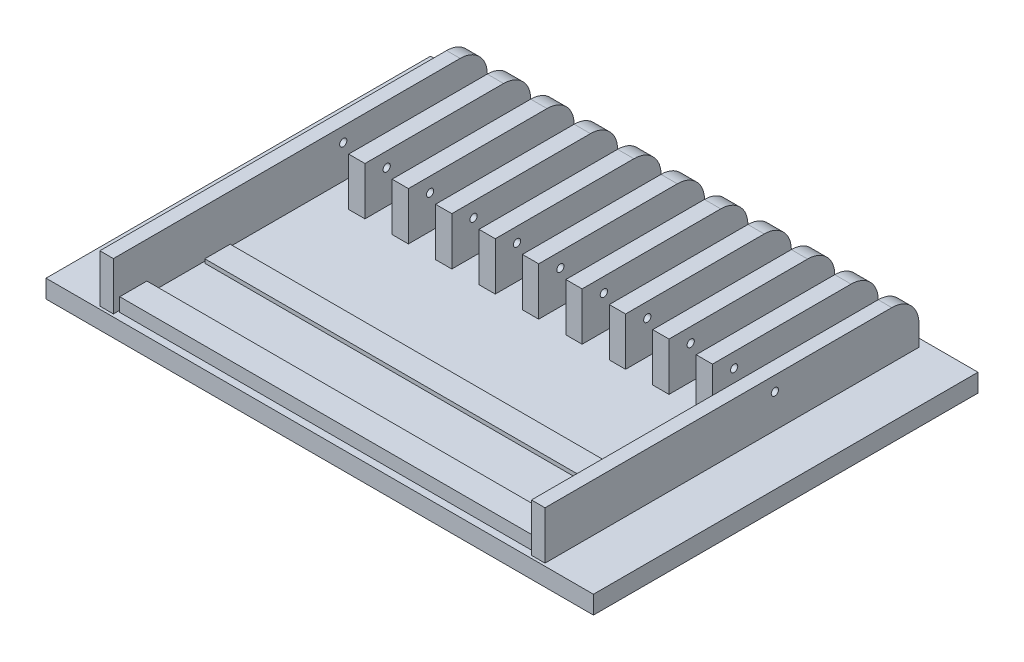
SolidWorks part; units mm, degrees
material "Maple"
ref_plane "Front Plane" through (0, 0, 0) normal (0, 0, 1) x (1, 0, 0)
ref_plane "Top Plane" through (0, 0, 0) normal (0, 1, 0) x (1, 0, 0)
ref_plane "Right Plane" through (0, 0, 0) normal (1, 0, 0) x (0, 0, -1)
sketch "Sketch1" plane through (0, 0, 0) normal (0, 1, 0) x (1, 0, 0)
  line L1 (302.5, -212.5) -> (-302.5, -212.5)
  line L2 (302.5, -212.5) -> (302.5, 212.5)
  line L3 (302.5, 212.5) -> (-302.5, 212.5)
  line L4 (-302.5, -212.5) -> (-302.5, 212.5)
  line L5 (302.5, -212.5) -> (-302.5, 212.5) construction
  line L6 (302.5, 212.5) -> (-302.5, -212.5) construction
  point P0 (0, 0)
  dimension "D1" = 605
  dimension "D2" = 425
extrude "Boss-Extrude1" add sketch "Sketch1" against normal blind 20
sketch "Sketch2" plane through (0, 0, 0) normal (1, 0, 0) x (0, 0, -1)
  line L0 (-212.5, -20) -> (-212.5, 0) construction
  line L1 (203.7, 0) -> (-209.5, 0)
  line L2 (203.7, 0) -> (203.7, 23)
  line L3 (173.7, 53) -> (-209.5, 53)
  line L4 (-209.5, 0) -> (-209.5, 53)
  line L5 (-212.5, 0) -> (212.5, 0) construction
  line L6 (212.5, -20) -> (212.5, 0) construction
  arc A0 (203.7, 23) -> (173.7, 53) centre (173.7, 23) ccw
  point P9 (0, 0)
  point P10 (194.2218, 0)
  dimension "D1" = 30
  dimension "D2" = 53
  dimension "D3" = 3
  dimension "D4" = 8.8
extrude "Boss-Extrude2" add sketch "Sketch2" along normal mid plane 492
sketch "Sketch3" plane through (0, 0, 209.5) normal (0, 0, 1) x (1, 0, 0)
  line L0 (246, 53) -> (-246, 53) construction
  line L1 (-231, 0) -> (-201, 0)
  line L2 (-231, 0) -> (-231, 53)
  line L3 (-231, 53) -> (-201, 53)
  line L4 (-201, 0) -> (-201, 53)
  line L5 (-231, 0) -> (-201, 53) construction
  line L6 (-231, 53) -> (-201, 0) construction
  line L7 (246, 0) -> (-246, 0) construction
  line L8 (0, 0) -> (0, 53) construction
  line L9 (-183, 0) -> (-183, 53)
  line L10 (-183, 53) -> (-153, 0) construction
  line L11 (-183, 0) -> (-153, 53) construction
  line L12 (-153, 0) -> (-153, 53)
  line L13 (-183, 53) -> (-153, 53)
  line L14 (-183, 0) -> (-153, 0)
  line L15 (-135, 0) -> (-135, 53)
  line L16 (-135, 53) -> (-105, 0) construction
  line L17 (-135, 0) -> (-105, 53) construction
  line L18 (-105, 0) -> (-105, 53)
  line L19 (-135, 53) -> (-105, 53)
  line L20 (-135, 0) -> (-105, 0)
  line L21 (-87, 0) -> (-87, 53)
  line L22 (-87, 53) -> (-57, 0) construction
  line L23 (-87, 0) -> (-57, 53) construction
  line L24 (-57, 0) -> (-57, 53)
  line L25 (-87, 53) -> (-57, 53)
  line L26 (-87, 0) -> (-57, 0)
  line L27 (-39, 0) -> (-39, 53)
  line L28 (-39, 53) -> (-9, 0) construction
  line L29 (-39, 0) -> (-9, 53) construction
  line L30 (-9, 0) -> (-9, 53)
  line L31 (-39, 53) -> (-9, 53)
  line L32 (-39, 0) -> (-9, 0)
  line L33 (9, 0) -> (9, 53)
  line L34 (9, 53) -> (39, 0) construction
  line L35 (9, 0) -> (39, 53) construction
  line L36 (39, 0) -> (39, 53)
  line L37 (9, 53) -> (39, 53)
  line L38 (9, 0) -> (39, 0)
  line L39 (57, 0) -> (57, 53)
  line L40 (57, 53) -> (87, 0) construction
  line L41 (57, 0) -> (87, 53) construction
  line L42 (87, 0) -> (87, 53)
  line L43 (57, 53) -> (87, 53)
  line L44 (57, 0) -> (87, 0)
  line L45 (105, 0) -> (105, 53)
  line L46 (105, 53) -> (135, 0) construction
  line L47 (105, 0) -> (135, 53) construction
  line L48 (135, 0) -> (135, 53)
  line L49 (105, 53) -> (135, 53)
  line L50 (105, 0) -> (135, 0)
  line L51 (153, 0) -> (153, 53)
  line L52 (153, 53) -> (183, 0) construction
  line L53 (153, 0) -> (183, 53) construction
  line L54 (183, 0) -> (183, 53)
  line L55 (153, 53) -> (183, 53)
  line L56 (153, 0) -> (183, 0)
  line L57 (201, 0) -> (201, 53)
  line L58 (201, 53) -> (231, 0) construction
  line L59 (201, 0) -> (231, 53) construction
  line L60 (231, 0) -> (231, 53)
  line L61 (201, 53) -> (231, 53)
  line L62 (201, 0) -> (231, 0)
  line L63 (-216, 26.5) -> (-168, 26.5) construction
  line L64 (0, 53) -> (-9, 53) construction
  line L65 (0, 53) -> (9, 53) construction
  point P0 (-216, 26.5)
  point P12 (-168, 26.5)
  point P18 (-120, 26.5)
  point P23 (-72, 26.5)
  point P28 (-24, 26.5)
  point P33 (24, 26.5)
  point P38 (72, 26.5)
  point P43 (120, 26.5)
  point P48 (168, 26.5)
  point P53 (216, 26.5)
  dimension "D1" = 30
  dimension "D3" = 48
  dimension "D2" = 10
extrude "Cut-Extrude1" cut sketch "Sketch3" against normal through all
sketch "Sketch4" plane through (-246, 0, 0) normal (-1, 0, 0) x (0, 0, 1)
  line L0 (209.5, 0) -> (-203.7, 0) construction
  line L1 (209.5, 53) -> (209.5, 0) construction
  circle A0 centre (-44.5, 37) radius 4
  dimension "D1" = 37
  dimension "D2" = 254
  dimension "D3" = 8
extrude "Cut-Extrude2" cut sketch "Sketch4" against normal through all
sketch "Sketch5" plane through (0, 0, 0) normal (1, 0, 0) x (0, 0, -1)
  line L0 (-212.5, 0) -> (212.5, 0) construction
  line L1 (-209.5, 53) -> (20.5, 53)
  line L2 (-209.5, 53) -> (-209.5, 0)
  line L3 (-209.5, 0) -> (20.5, 0)
  line L4 (20.5, 53) -> (20.5, 0)
  dimension "D1" = 230
extrude "Cut-Extrude3" cut sketch "Sketch5" against normal mid plane 440
sketch "Sketch6" plane through (0, 0, 0) normal (0, 1, 0) x (1, 0, 0)
  line L0 (0, 0) -> (0, -212.5) construction
  line L1 (-302.5, -212.5) -> (302.5, -212.5) construction
  line L2 (-231, -209.5) -> (-246, -209.5) construction
  line L3 (229, -174.5) -> (-229, -174.5)
  line L4 (229, -174.5) -> (229, -204.5)
  line L5 (229, -204.5) -> (-229, -204.5)
  line L6 (-229, -174.5) -> (-229, -204.5)
  line L7 (229, -174.5) -> (-229, -204.5) construction
  line L8 (229, -204.5) -> (-229, -174.5) construction
  line L9 (-231, 173.7) -> (-231, -209.5) construction
  point P5 (0, -189.5)
  dimension "D1" = 5
  dimension "D2" = 30
  dimension "D3" = 2
extrude "Boss-Extrude3" add sketch "Sketch6" along normal blind 15
sketch "Sketch7" plane through (0, 0, 0) normal (0, 1, 0) x (1, 0, 0)
  line L0 (0, 0) -> (0, -174.5) construction
  line L1 (229, -174.5) -> (-229, -174.5) construction
  line L3 (-229, -82.5) -> (229, -82.5)
  line L4 (-229, -82.5) -> (-229, -110.5)
  line L5 (-229, -110.5) -> (229, -110.5)
  line L6 (229, -82.5) -> (229, -110.5)
  line L7 (-229, -82.5) -> (229, -110.5) construction
  line L8 (-229, -110.5) -> (229, -82.5) construction
  line L9 (-229, -174.5) -> (-229, -204.5) construction
  point P5 (0, -96.5)
  point P10 (0, 0)
  dimension "D1" = 28
  dimension "D2" = 92
extrude "Boss-Extrude4" add sketch "Sketch7" along normal blind 4.3
